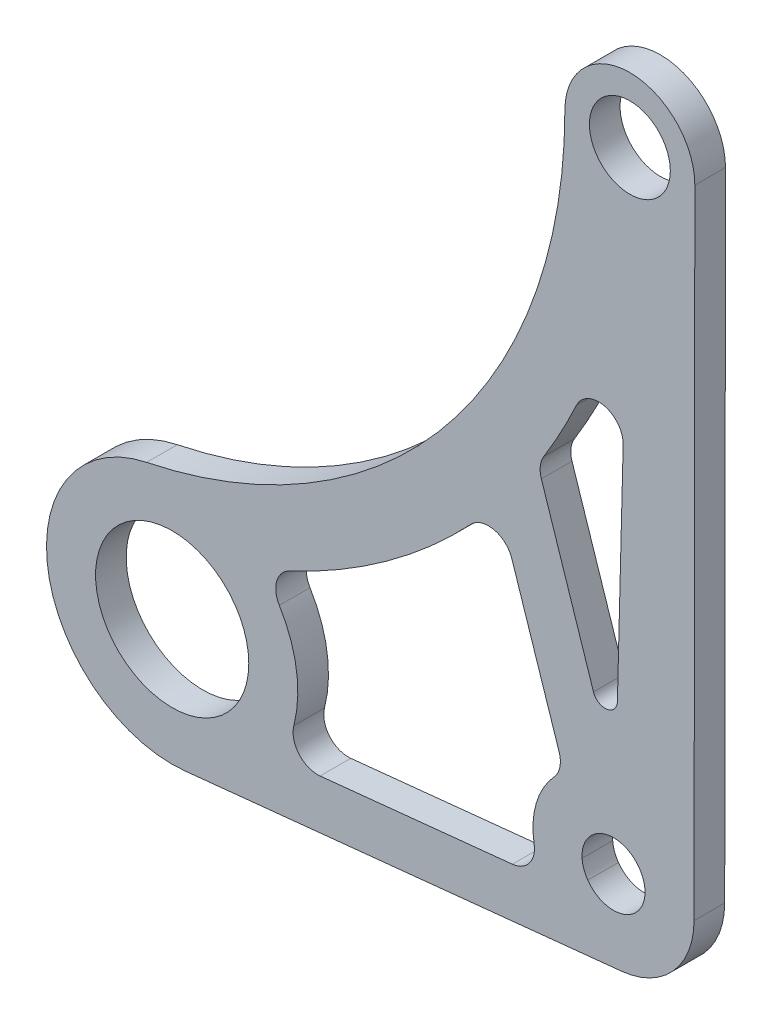
SolidWorks part; units mm, degrees
material "6061-T6 (SS)"
ref_plane "Front Plane" through (0, 0, 0) normal (0, 0, 1) x (1, 0, 0)
ref_plane "Top Plane" through (0, 0, 0) normal (0, 1, 0) x (1, 0, 0)
ref_plane "Right Plane" through (0, 0, 0) normal (1, 0, 0) x (0, 0, -1)
sketch "Sketch2" plane through (0, 0, 0) normal (0, 0, 1) x (1, 0, 0)
  line L0 (0, 0) -> (45.72, 0) construction
  line L1 (45.72, 0) -> (47.4133, 66.0183) construction
  line L2 (47.4133, 66.0183) -> (0, 0) construction
  line L3 (-9.9543, 8.3886) -> (42.2663, 70.3558)
  line L4 (54.1443, 66.0101) -> (54.0639, -0.0102)
  line L5 (46.5729, -8.3002) -> (1.3307, -12.9493)
  line L6 (-6.2268, 4.9225) -> (44.1256, 68.6173)
  line L7 (0.8114, -7.8959) -> (46.0536, -3.2468)
  line L8 (48.9813, -0.1295) -> (51.601, 65.852)
  line L9 (40.6823, 66.0183) -> (40.6823, 38.0486)
  line L10 (45.72, 0) -> (38.8832, 9.7026) construction
  line L11 (45.72, 0) -> (42.0108, 11.275) construction
  line L12 (45.72, 0) -> (44.9726, 11.8459) construction
  line L13 (47.2407, 59.2895) -> (45.9339, 8.3412)
  line L14 (45.72, 0) -> (35.8732, 29.9315) construction
  line L15 (33.8001, 27.2416) -> (40.5957, 6.585)
  line L16 (37.8709, 32.8508) -> (45.9339, 8.3412)
  line L17 (40.7966, 14.9657) -> (38.1275, 14.0877) construction
  line L18 (40.7966, 14.9657) -> (43.4657, 15.8438) construction
  circle A0 centre (0, 0) radius 7.9375
  circle A1 centre (45.72, 0) radius 3.2639
  circle A2 centre (47.4133, 66.0183) radius 4.191
  circle A3 centre (0, 0) radius 13.0175
  circle A4 centre (45.72, 0) radius 8.3439
  circle A5 centre (47.4133, 66.0183) radius 6.731
  circle A6 centre (-13.7313, 66.0183) radius 54.4137
  circle A7 centre (-13.7313, 66.0183) radius 61.3423
  point P29 (47.2407, 59.2895)
  point P30 (45.72, 0)
  dimension "D1" = 8.382
  dimension "D2" = 6.5278
  dimension "D3" = 15.875
  dimension "2.7" = 45.72
  dimension "D5" = 66.04
  dimension "D6" = 5.08
  dimension "D7" = 2.54
  dimension "D8" = 5.08
  dimension "D9" = 81.28
  dimension "D4" = 54.83
  dimension "D10" = 71.79
  dimension "D11" = 86.39
extrude "Boss-Extrude1" add sketch "Sketch2" along normal blind 3.175 contours A2 A7 A5 L6 | A7 A2 L8 A5 | A7 A5 L8 A2 | A5 A7 A2 L6 | A5 L9 L6 | A6 L6 L9 | A3 A7 A5 L6 A6 | A5 L8 A4 L4 | A5 L13 A4 L8 | A4 L8 A1 L7 | L8 A4 L7 A1 | A4 L7 A3 L5 | A7 A3 L7 A0 L6 | A7 A0 L7 A3 | L6 A7 A0 A3 | A3 A7 L6 | A7 L15 A4 L16 | A6 A3 L6 | A7 L6 A0 region at (-6.2809, 8.6258, 0) region at (-0.391, 13.1481, 0) region at (-9.0611, 4.5514, 0) region at (2.354, 9.7942, 0) region at (29.4611, 32.3937, 0) region at (24.4956, -8.1948, 0) region at (43.7611, 69.4736, 0) region at (51.4426, 67.8107, 0) region at (-6.083, 5.1015, 0) region at (40.7364, 64.7852, 0) region at (40.6735, 64.6868, 0) region at (9.1953, 0.5362, 0) region at (48.3425, -2.463, 0) region at (43.9464, 62.5495, 0) region at (39.5798, 18.9244, 0) region at (42.7463, 2.7928, 0) region at (52.2253, 31.0661, 0) region at (48.5005, 34.7082, 0) region at (49.5829, 61.2881, 0)
ref_plane "Plane2" through (45.72, 0, 0) normal (-0.576, 0.8174, 0) x (0.8174, 0.576, 0)
split line "Split Line2"
ref_plane "Plane3" through (45.72, 0, 0) normal (-0.063, 0.998, 0) x (0.998, 0.063, 0)
split line "Split Line3"
fillet "Fillet1" radius 2.54 4 edges at (9.2611, 9.1481, 1.5875) (11.0749, -6.8412, 1.5875) (38.4148, -4.0318, 1.5875) (47.2407, 59.2895, 1.5875)
fillet "Fillet2" radius 2.54 3 edges at (40.5957, 6.585, 1.5875) (37.8709, 32.8508, 1.5875) (33.8001, 27.2416, 1.5875)
fillet "Fillet3" radius 1.27 1 edges at (45.9339, 8.3412, 1.5875)
equation "\"Droop angle\"= 54.83"
equation "\"Static angle\"= 71.79"
equation "\"Jounce angle\"= 86.39"
equation "\"D4@Sketch2\"=\"Droop angle\""
equation "\"D10@Sketch2\"=\"Static angle\""
equation "\"D11@Sketch2\"=\"Jounce angle\""
